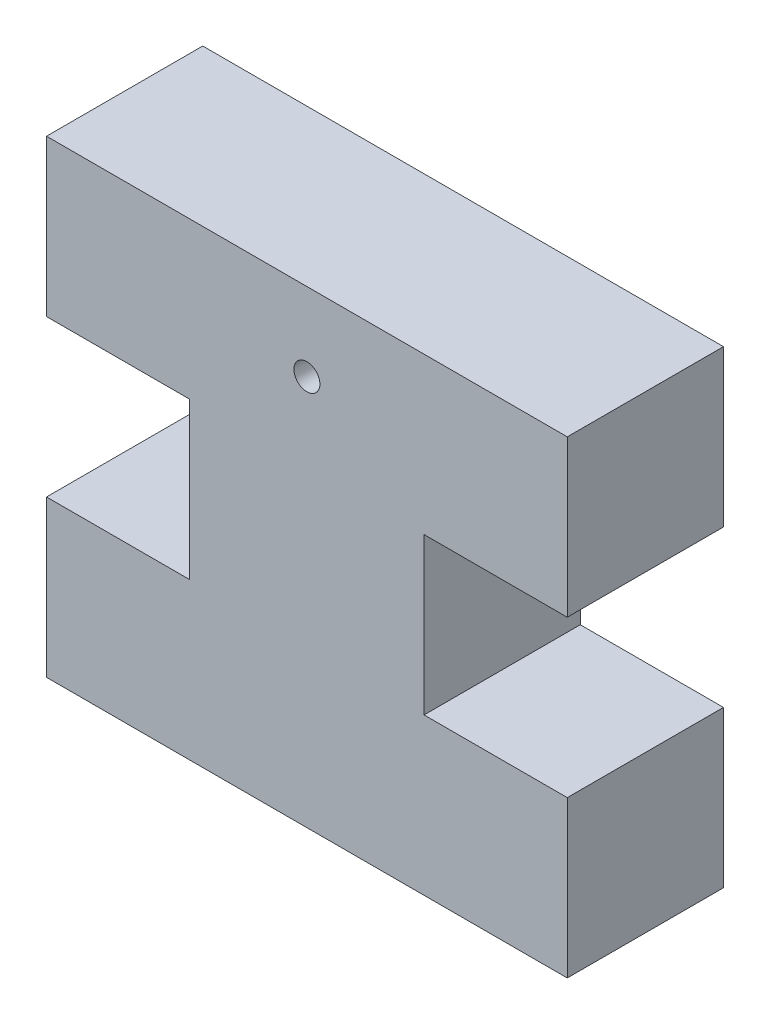
SolidWorks part; units mm, degrees
ref_plane "Front Plane" through (0, 0, 0) normal (0, 0, 1) x (1, 0, 0)
ref_plane "Top Plane" through (0, 0, 0) normal (0, 1, 0) x (1, 0, 0)
ref_plane "Right Plane" through (0, 0, 0) normal (1, 0, 0) x (0, 0, -1)
sketch "Sketch1" plane through (0, 0, 0) normal (0, 0, 1) x (1, 0, 0)
  line L1 (0, 0) -> (9, 0)
  line L2 (0, 0) -> (0, 6)
  line L4 (9, 0) -> (9, 6)
  line L5 (14.5, 12) -> (14.5, 6)
  line L6 (14.5, 6) -> (9, 6)
  line L7 (-5.5, 12) -> (-5.5, 6)
  line L8 (14.5, 12) -> (-5.5, 6) construction
  line L9 (14.5, 6) -> (-5.2679, 11.9304) construction
  line L10 (0, 6) -> (-5.5, 6)
  line L14 (-5.5, 12) -> (14.5, 12)
  circle A1 centre (4.5, 9) radius 0.5
  point P7 (4.5, 0)
  dimension "D3" = 1
  dimension "D4" = 3
  dimension "D1" = 9
  dimension "D2" = 6
  dimension "D5" = 6
  dimension "D7" = 20
extrude "Boss-Extrude1" add sketch "Sketch1" along normal blind 6
sketch "Sketch2" plane through (0, 0, 0) normal (0, -1, 0) x (1, 0, 0)
  line L0 (4.5, 0) -> (4.5, 6) construction
  line L1 (-5.5, 6) -> (14.5, 6)
  line L2 (-5.5, 6) -> (-5.5, 0)
  line L3 (-5.5, 0) -> (14.5, 0)
  line L4 (14.5, 6) -> (14.5, 0)
  line L5 (-5.5, 6) -> (14.5, 0) construction
  line L6 (-5.5, 0) -> (14.5, 6) construction
  line L7 (0, 0) -> (9, 0) construction
  point P0 (4.5, 3)
  point P9 (4.5, 0)
  dimension "D1" = 20
  dimension "D2" = 6
extrude "Boss-Extrude2" add sketch "Sketch2" along normal blind 6
